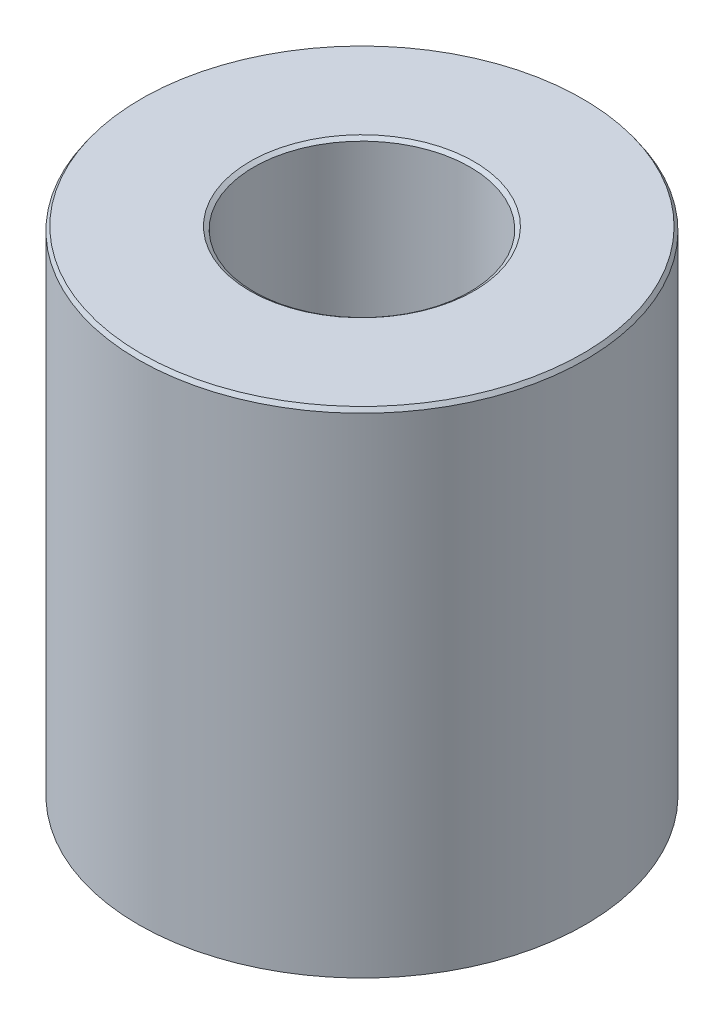
SolidWorks part; units mm, degrees
ref_plane "Front Plane" through (0, 0, 0) normal (0, 0, 1) x (1, 0, 0)
ref_plane "Top Plane" through (0, 0, 0) normal (0, 1, 0) x (1, 0, 0)
ref_plane "Right Plane" through (0, 0, 0) normal (1, 0, 0) x (0, 0, -1)
sketch "Sketch1" plane through (0, 0, 0) normal (0, 1, 0) x (1, 0, 0)
  circle A0 centre (0, 0) radius 50
  dimension "SLEEVE_OD" = 100
extrude "Boss-Extrude1" add sketch "Sketch1" along normal blind 110.9405
sketch "Sketch2" plane through (0, 0, 0) normal (0, 1, 0) x (1, 0, 0)
  circle A0 centre (0, 0) radius 24.1839
  dimension "BORE_D" = 48.3679
extrude "Cut-Extrude1" cut sketch "Sketch2" along normal through all
chamfer "Chamfer1" distance 0.8945 angle 34.352 4 edges at (0, 110.9405, 24.1839) (0, 0, 24.1839) (0, 0, 50) (0, 110.9405, 50) first distance on face at (0, 110.9405, 24.1839) first distance on face at (0, 0, 24.1839) first distance on face at (0, 110.9405, 50)
